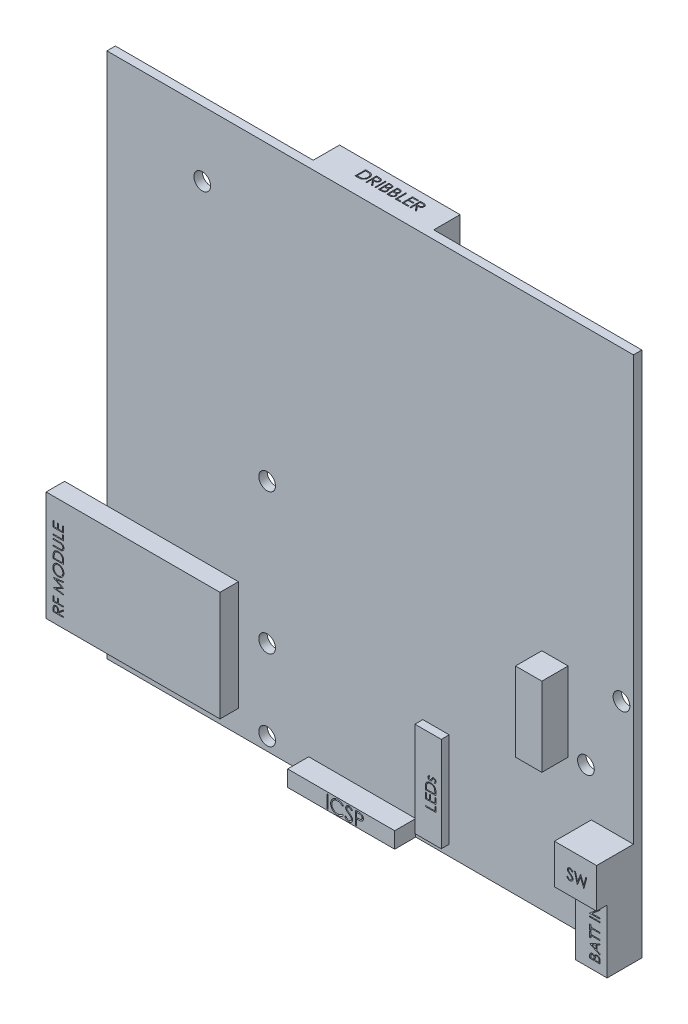
SolidWorks part; units mm, degrees
ref_plane "Front Plane" through (0, 0, 0) normal (0, 0, 1) x (1, 0, 0)
ref_plane "Top Plane" through (0, 0, 0) normal (0, 1, 0) x (1, 0, 0)
ref_plane "Right Plane" through (0, 0, 0) normal (1, 0, 0) x (0, 0, -1)
sketch "Sketch1" plane through (0, 0, 0) normal (0, 0, 1) x (1, 0, 0)
  line L1 (-25.0277, 9.5656) -> (74.9723, 9.5656)
  line L2 (-25.0277, 9.5656) -> (-25.0277, -90.4344)
  line L3 (-25.0277, -90.4344) -> (74.9723, -90.4344)
  line L4 (74.9723, 9.5656) -> (74.9723, -90.4344)
  dimension "D1" = 100
  dimension "D2" = 100
extrude "Boss-Extrude1" add sketch "Sketch1" along normal blind 1.6
sketch "Sketch2" plane through (0, 0, 1.6) normal (0, 0, 1) x (1, 0, 0)
  line L0 (-25.0277, -90.4344) -> (74.9723, -90.4344) construction
  line L1 (-33.0777, -65.2594) -> (-0.0527, -65.2594)
  line L2 (-33.0777, -65.2594) -> (-33.0777, -86.0844)
  line L3 (-33.0777, -86.0844) -> (-0.0527, -86.0844)
  line L4 (-0.0527, -65.2594) -> (-0.0527, -86.0844)
  line L6 (-25.0277, 9.5656) -> (-25.0277, -90.4344) construction
  dimension "D1" = 33.025
  dimension "D2" = 20.825
  dimension "D3" = 4.35
  dimension "D4" = 8.05
extrude "Boss-Extrude2" add sketch "Sketch2" along normal blind 3.5
sketch "Sketch3" plane through (0, 0, 0) normal (0, 0, -1) x (-1, 0, 0)
  line L0 (25.0277, 9.5656) -> (25.0277, -90.4344) construction
  line L1 (-39.4463, -37.1604) -> (-7.4463, -37.1604)
  line L2 (-39.4463, -37.1604) -> (-39.4463, -43.1604)
  line L3 (-39.4463, -43.1604) -> (-7.4463, -43.1604)
  line L4 (-7.4463, -37.1604) -> (-7.4463, -43.1604)
  line L5 (-74.9723, 9.5656) -> (25.0277, 9.5656) construction
  dimension "D1" = 32
  dimension "D2" = 6
  dimension "D3" = 32.474
  dimension "D4" = 46.726
extrude "Boss-Extrude3" add sketch "Sketch3" along normal blind 5
sketch "Sketch4" plane through (0, 0, 1.6) normal (0, 0, 1) x (1, 0, 0)
  line L0 (-25.0277, -86.0844) -> (-25.0277, -90.4344) construction
  line L1 (13.2963, -87.3844) -> (33.6213, -87.3844)
  line L2 (13.2963, -87.3844) -> (13.2963, -90.4344)
  line L3 (13.2963, -90.4344) -> (33.6213, -90.4344)
  line L4 (33.6213, -87.3844) -> (33.6213, -90.4344)
  line L5 (-25.0277, -90.4344) -> (74.9723, -90.4344) construction
  dimension "D1" = 3.05
  dimension "D2" = 38.324
  dimension "D3" = 20.325
extrude "Boss-Extrude4" add sketch "Sketch4" along normal blind 4
sketch "Sketch5" plane through (0, 0, 1.6) normal (0, 0, 1) x (1, 0, 0)
  line L0 (74.9723, -90.4344) -> (74.9723, 9.5656) construction
  line L1 (68.9723, -78.4344) -> (74.9723, -78.4344)
  line L2 (68.9723, -78.4344) -> (68.9723, -90.4344)
  line L3 (68.9723, -90.4344) -> (74.9723, -90.4344)
  line L4 (74.9723, -78.4344) -> (74.9723, -90.4344)
  line L5 (33.6213, -90.4344) -> (74.9723, -90.4344) construction
  dimension "D1" = 6
  dimension "D2" = 12
extrude "Boss-Extrude5" add sketch "Sketch5" along normal blind 5
sketch "Sketch6" plane through (0, 0, 6.6) normal (0, 0, 1) x (1, 0, 0)
  line L0 (73.6619, -89.0757) -> (73.6619, -81.0753) construction
  text T0 "BATT IN" font "Century Gothic" height 2
extrude "Cut-Extrude1" cut sketch "Sketch6" against normal blind 1
sketch "Sketch7" plane through (0, 0, 5.1) normal (0, 0, 1) x (1, 0, 0)
  line L0 (-29.7567, -84.5425) -> (-29.7567, -66.8173) construction
  text T0 "RF MODULE" font "Century Gothic" height 2
sketch "Sketch8" plane through (0, 0, 5.6) normal (0, 0, 1) x (1, 0, 0)
  text T0 "ICSP" font "Century Gothic" height 2.5
extrude "Cut-Extrude2" cut sketch "Sketch8" against normal blind 1
sketch "Sketch9" plane through (0, 0, 1.6) normal (0, 0, 1) x (1, 0, 0)
  line L0 (74.9723, -78.4344) -> (74.9723, 9.5656) construction
  line L1 (57.5723, -47.8094) -> (62.5723, -47.8094)
  line L2 (57.5723, -47.8094) -> (57.5723, -62.8094)
  line L3 (57.5723, -62.8094) -> (62.5723, -62.8094)
  line L4 (62.5723, -47.8094) -> (62.5723, -62.8094)
  line L5 (33.6213, -90.4344) -> (68.9723, -90.4344) construction
  dimension "D1" = 15
  dimension "D2" = 5
  dimension "D3" = 12.4
  dimension "D4" = 27.625
extrude "Boss-Extrude7" add sketch "Sketch9" along normal blind 5
sketch "Sketch11" plane through (0, 0, 0) normal (0, 0, -1) x (-1, 0, 0)
  line L0 (25.0277, 9.5656) -> (25.0277, -90.4344) construction
  line L1 (-35.4463, 9.5656) -> (-12.5463, 9.5656)
  line L2 (-35.4463, 9.5656) -> (-35.4463, 3.0656)
  line L3 (-35.4463, 3.0656) -> (-12.5463, 3.0656)
  line L4 (-12.5463, 9.5656) -> (-12.5463, 3.0656)
  line L5 (-74.9723, 9.5656) -> (25.0277, 9.5656) construction
  dimension "D1" = 37.574
  dimension "D2" = 6.5
  dimension "D3" = 22.9
extrude "Boss-Extrude8" add sketch "Sketch11" along normal blind 5
sketch "Sketch12" plane through (0, 9.5656, 0) normal (0, 1, 0) x (1, 0, 0)
  text T0 "DRIBBLER" font "Century Gothic" height 2
extrude "Cut-Extrude3" cut sketch "Sketch12" against normal blind 1
sketch "Sketch13" plane through (0, 0, 1.6) normal (0, 0, 1) x (1, 0, 0)
  line L0 (-25.0277, 9.5656) -> (-25.0277, -65.2594) construction
  line L1 (74.9723, 9.5656) -> (-25.0277, 9.5656) construction
  circle A0 centre (-6.9277, -2.8344) radius 1.5875
  circle A1 centre (72.6963, -48.5594) radius 1.5875
  circle A2 centre (5.3923, -46.0044) radius 1.5875
  circle A3 centre (5.3923, -72.6844) radius 1.5875
  circle A4 centre (5.3923, -87.9344) radius 1.5875
  circle A5 centre (65.9473, -62.3844) radius 1.5875
  dimension "D1" = 3.175
  dimension "D2" = 3.175
  dimension "D3" = 3.175
  dimension "D4" = 3.175
  dimension "D5" = 3.175
  dimension "D6" = 3.175
  dimension "D7" = 18.1
  dimension "D8" = 12.4
  dimension "D9" = 30.42
  dimension "D10" = 55.57
  dimension "D11" = 30.42
  dimension "D12" = 30.42
  dimension "D13" = 82.25
  dimension "D14" = 97.5
  dimension "D15" = 90.975
  dimension "D16" = 71.95
  dimension "D17" = 97.724
  dimension "D18" = 58.125
extrude "Cut-Extrude5" cut sketch "Sketch13" against normal through all
sketch "Sketch14" plane through (0, 0, 1.6) normal (0, 0, 1) x (1, 0, 0)
  line L0 (-25.0277, 9.5656) -> (-25.0277, -65.2594) construction
  line L1 (34.9723, -70.4344) -> (39.9723, -70.4344)
  line L2 (34.9723, -70.4344) -> (34.9723, -88.4344)
  line L3 (34.9723, -88.4344) -> (39.9723, -88.4344)
  line L4 (39.9723, -70.4344) -> (39.9723, -88.4344)
  line L5 (74.9723, 9.5656) -> (-25.0277, 9.5656) construction
  dimension "D1" = 60
  dimension "D2" = 80
  dimension "D3" = 5
  dimension "D4" = 18
extrude "Boss-Extrude9" add sketch "Sketch14" along normal blind 1.5
sketch "Sketch15" plane through (0, 0, 3.1) normal (0, 0, 1) x (1, 0, 0)
  line L0 (38.9424, -83.2391) -> (38.9424, -73.3783) construction
  text T0 "LEDs" font "Century Gothic" height 2
extrude "Cut-Extrude6" cut sketch "Sketch15" against normal blind 1
sketch "Sketch16" plane through (0, 0, 1.6) normal (0, 0, 1) x (1, 0, 0)
  line L0 (33.6213, -90.4344) -> (68.9723, -90.4344) construction
  line L1 (66.9723, -70.9344) -> (74.9723, -70.9344)
  line L2 (66.9723, -70.9344) -> (66.9723, -78.4344)
  line L3 (66.9723, -78.4344) -> (74.9723, -78.4344)
  line L4 (74.9723, -70.9344) -> (74.9723, -78.4344)
  line L5 (74.9723, -78.4344) -> (74.9723, 9.5656) construction
  dimension "D1" = 8
  dimension "D2" = 7.5
  dimension "D3" = 12
extrude "Boss-Extrude11" add sketch "Sketch16" along normal blind 7
sketch "Sketch17" plane through (0, 0, 8.6) normal (0, 0, 1) x (1, 0, 0)
  text T0 "SW" font "Century Gothic" height 2
extrude "Cut-Extrude7" cut sketch "Sketch17" against normal blind 1
extrude "Cut-Extrude8" cut sketch "Sketch7" against normal blind 1
